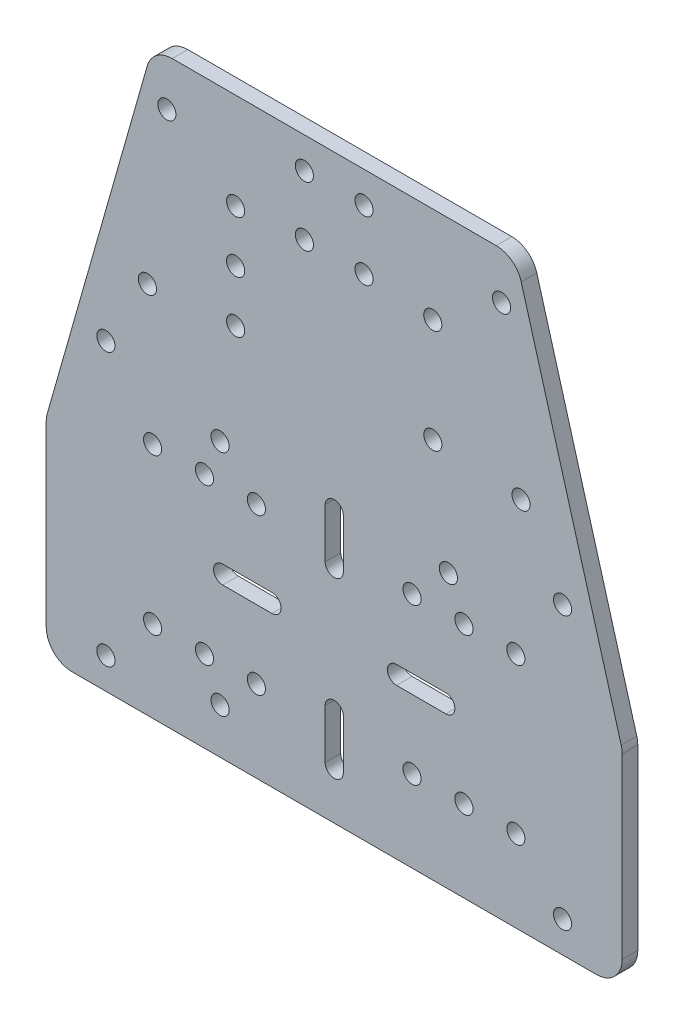
SolidWorks part; units mm, degrees
ref_plane "前视基准面" through (0, 0, 0) normal (0, 0, 1) x (1, 0, 0)
ref_plane "上视基准面" through (0, 0, 0) normal (0, 1, 0) x (1, 0, 0)
ref_plane "右视基准面" through (0, 0, 0) normal (1, 0, 0) x (0, 0, -1)
sketch "草图1" plane through (0, 0, 0) normal (0, 0, 1) x (1, 0, 0)
  line L0 (-55.5, 0) -> (-55.5, -40)
  line L1 (-55.5, -40) -> (55.5, -40)
  line L2 (55.5, -40) -> (55.5, 0)
  line L3 (55.5, 0) -> (35, 72)
  line L4 (35, 72) -> (-35, 72)
  line L5 (-35, 72) -> (-55.5, 0)
  line L6 (0, 0) -> (0, -40) construction
  dimension "D1" = 111
  dimension "D2" = 112
  dimension "D3" = 40
  dimension "D4" = 70
extrude "凸台-拉伸1" add sketch "草图1" along normal blind 3 contours L4 L5 L0 L1 L2 L3
sketch "草图2" plane through (0, 0, 3) normal (0, 0, 1) x (1, 0, 0)
  line L0 (0, 0) -> (0, -15.5) construction
  line L1 (0, -9.25) -> (12, -9.25) construction
  line L2 (0, -21.25) -> (0, -30.75) construction
  line L3 (1.75, -21.25) -> (1.75, -30.75)
  line L4 (-1.75, -21.25) -> (-1.75, -30.75)
  line L5 (12, -9.25) -> (21.5, -9.25) construction
  line L6 (12, -7.5) -> (21.5, -7.5)
  line L7 (12, -11) -> (21.5, -11)
  line L8 (0, 2.75) -> (0, 12.25) construction
  line L9 (1.75, 2.75) -> (1.75, 12.25)
  line L10 (-1.75, 2.75) -> (-1.75, 12.25)
  line L11 (-12, -9.25) -> (-21.5, -9.25) construction
  line L12 (-12, -7.5) -> (-21.5, -7.5)
  line L13 (-12, -11) -> (-21.5, -11)
  line L14 (-32.25, 63) -> (32.25, 63) construction
  line L15 (-55.5, -40) -> (55.5, -40) construction
  line L16 (-5.75, 66) -> (5.75, 66) construction
  line L18 (-44, 18.5) -> (44, 18.5) construction
  line L19 (-44, 18.5) -> (-44, -34) construction
  line L20 (-44, -34) -> (44, -34) construction
  line L21 (44, 18.5) -> (44, -34) construction
  line L22 (-44, 18.5) -> (44, -34) construction
  line L23 (-15, 5.75) -> (15, 5.75) construction
  line L24 (-15, 5.75) -> (-15, -24.25) construction
  line L25 (-15, -24.25) -> (15, -24.25) construction
  line L26 (15, 5.75) -> (15, -24.25) construction
  line L27 (-15, 5.75) -> (15, -24.25) construction
  line L28 (-15, -24.25) -> (15, 5.75) construction
  line L29 (-22, 12.75) -> (22, 12.75) construction
  line L30 (-22, 12.75) -> (-22, -31.25) construction
  line L31 (-22, -31.25) -> (22, -31.25) construction
  line L32 (22, 12.75) -> (22, -31.25) construction
  line L33 (-22, 12.75) -> (22, -31.25) construction
  line L34 (-22, -31.25) -> (22, 12.75) construction
  line L35 (-5.75, 66) -> (-5.75, 54.5) construction
  line L36 (-5.75, 54.5) -> (5.75, 54.5) construction
  line L37 (5.75, 66) -> (5.75, 54.5) construction
  line L38 (-5.75, 66) -> (5.75, 54.5) construction
  line L39 (-5.75, 54.5) -> (5.75, 66) construction
  line L40 (32.25, 63) -> (36, 32) construction
  line L41 (36, 32) -> (-36, 32) construction
  line L42 (-36, 32) -> (-32.25, 63) construction
  line L44 (35, 72) -> (-35, 72) construction
  line L45 (0, 72) -> (0, 63) construction
  line L46 (-44, -34) -> (44, 18.5) construction
  line L47 (-19, 53.5) -> (19, 53.5) construction
  line L48 (-19, 53.5) -> (-19, 33.5) construction
  line L49 (-19, 33.5) -> (19, 33.5) construction
  line L50 (19, 53.5) -> (19, 33.5) construction
  line L51 (-19, 53.5) -> (19, 33.5) construction
  line L52 (-19, 33.5) -> (19, 53.5) construction
  arc A0 (1.75, -21.25) -> (-1.75, -21.25) centre (0, -21.25) ccw
  arc A1 (-1.75, -30.75) -> (1.75, -30.75) centre (0, -30.75) ccw
  arc A2 (12, -7.5) -> (12, -11) centre (12, -9.25) ccw
  arc A3 (21.5, -11) -> (21.5, -7.5) centre (21.5, -9.25) ccw
  arc A4 (1.75, 2.75) -> (-1.75, 2.75) centre (0, 2.75) cw
  arc A5 (-1.75, 12.25) -> (1.75, 12.25) centre (0, 12.25) cw
  arc A6 (-12, -7.5) -> (-12, -11) centre (-12, -9.25) cw
  arc A7 (-21.5, -11) -> (-21.5, -7.5) centre (-21.5, -9.25) cw
  point P7 (0, -26)
  point P12 (16.75, -9.25)
  point P20 (0, 7.5)
  point P27 (-16.75, -9.25)
  point P34 (0, -7.75)
  point P38 (0, 60.25)
  point P60 (0, 43.5)
  dimension "D4" = 24
  dimension "D5" = 24
  dimension "D6" = 30
  dimension "D9" = 44
  dimension "D1" = 3.5
  dimension "D2" = 9.5
  dimension "D3" = 30.75
  dimension "D7" = 6
  dimension "D8" = 52.5
  dimension "D10" = 30
  dimension "D11" = 44
  dimension "D12" = 11.5
  dimension "D13" = 11.5
  dimension "D14" = 6
  dimension "D15" = 9
  dimension "D16" = 64.5
  dimension "D17" = 72
  dimension "D18" = 40
  dimension "D19" = 88
  dimension "D20" = 20
  dimension "D21" = 38
  dimension "D22" = 18.5
hole_wizard "Ø3.5 (3.5) 直径孔1" positions "草图4" profile "草图5" hole size "Ø3.5" standard "Iso" end condition through all
sketch "草图4" plane through (0, 0, 3) normal (0, 0, 1) x (1, 0, 0)
  line L0 (-19, 53.5) -> (-19, 33.5) construction
  line L2 (-15, -24.25) -> (15, -24.25) construction
  point P0 (-5.75, 54.5)
  point P3 (5.75, 54.5)
  point P6 (5.75, 66)
  point P9 (-5.75, 66)
  point P12 (-32.25, 63)
  point P15 (-36, 32)
  point P18 (36, 32)
  point P21 (32.25, 63)
  point P24 (-44, 18.5)
  point P27 (44, 18.5)
  point P30 (44, -34)
  point P33 (-44, -34)
  point P36 (-22, -31.25)
  point P39 (-15, -24.25)
  point P42 (15, -24.25)
  point P45 (15, 5.75)
  point P48 (-15, 5.75)
  point P51 (-22, 12.75)
  point P56 (22, 12.75)
  point P59 (-19, 53.5)
  point P62 (-19, 43.5)
  point P66 (-19, 33.5)
  point P69 (19, 33.5)
  point P72 (19, 53.5)
  point P75 (-25, 5.75)
  point P77 (-25, -24.25)
  point P79 (-35, 5.75)
  point P81 (-35, -24.25)
  point P83 (25, 5.75)
  point P85 (35, 5.75)
  point P87 (35, -24.25)
  point P89 (25, -24.25)
  dimension "D1" = 20
  dimension "D2" = 10
  dimension "D3" = 10
  dimension "D4" = 10
sketch "草图5" plane through (-5.75, 54.5, 3) normal (1, 0, 0) x (0, -1, 0)
  line L0 (0, 0) -> (0, 3)
  line L1 (0, 3) -> (1.75, 3)
  line L2 (1.75, 3) -> (1.75, 0)
  line L5 (1.75, 0) -> (0, 0)
  line L11 (0, -6.35) -> (0, 107.95) construction
  dimension "通孔孔直径" = 3.5
  dimension "通孔孔深度" = 3
extrude "切除-拉伸1" cut sketch "草图2" against normal through all
fillet "圆角1" radius 5 6 edges at (-55.5, 0, 1.5) (-55.5, -40, 1.5) (55.5, -40, 1.5) (55.5, 0, 1.5) (35, 72, 1.5) (-35, 72, 1.5)
ref_axis "基准轴1" through (44, -34, 0) along (0, 0, 1)
